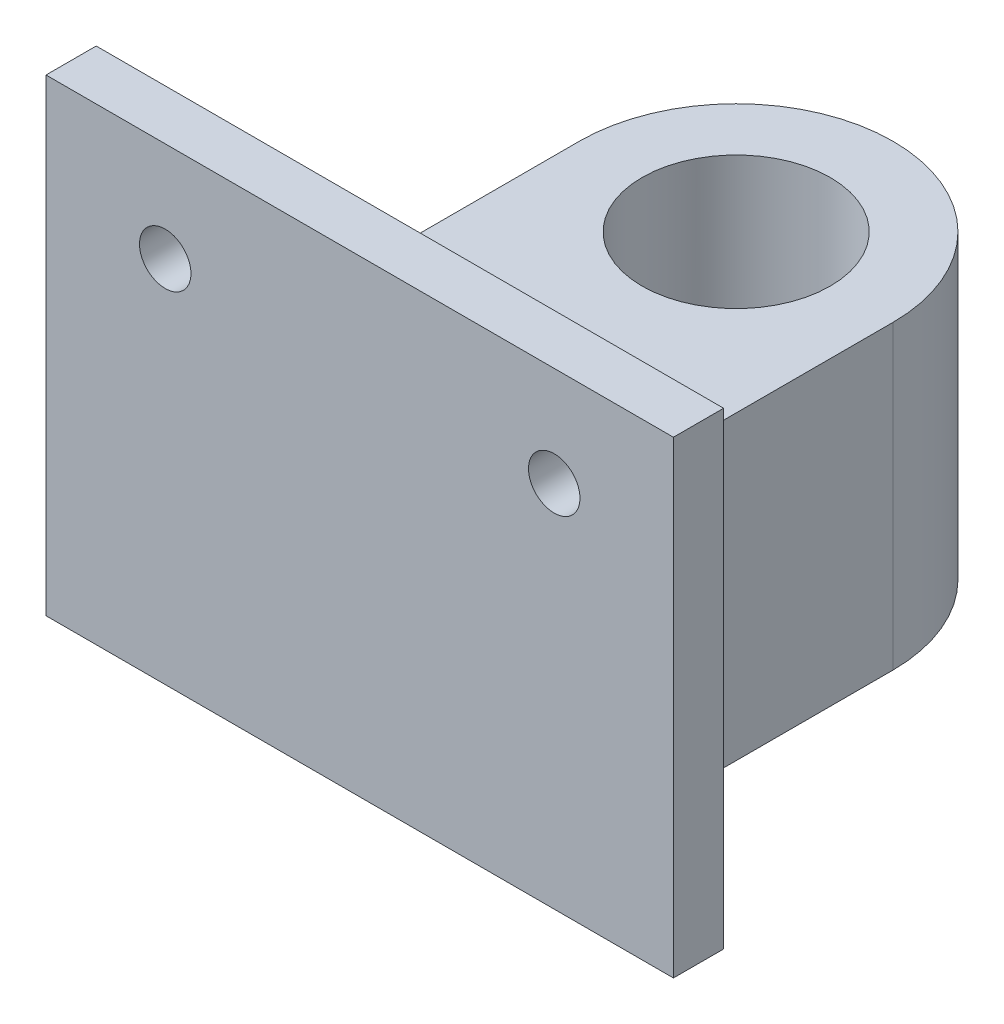
SolidWorks part; units mm, degrees
ref_plane "Front Plane" through (0, 0, 0) normal (0, 0, 1) x (1, 0, 0)
ref_plane "Top Plane" through (0, 0, 0) normal (0, 1, 0) x (1, 0, 0)
ref_plane "Right Plane" through (0, 0, 0) normal (1, 0, 0) x (0, 0, -1)
sketch "Profile-Sketch1" plane through (0, 0, 0) normal (0, 1, 0) x (1, 0, 0)
  line L0 (-25, -30) -> (25, -30)
  line L1 (25, -30) -> (25, -26)
  line L2 (-25, -30) -> (-25, -26)
  line L3 (-25, -26) -> (-22.5, -26)
  line L4 (-12.5, -16) -> (-12.5, 0)
  line L5 (25, -26) -> (22.5, -26)
  line L6 (12.5, -16) -> (12.5, 0)
  circle A0 centre (0, 0) radius 7.5
  arc A6 (12.5, 0) -> (-12.5, 0) centre (0, 0) ccw
  arc A7 (22.5, -26) -> (12.5, -16) centre (22.5, -16) cw
  arc A8 (-12.5, -16) -> (-22.5, -26) centre (-22.5, -16) cw
  dimension "D1" = 15
  dimension "D2" = 25
  dimension "D7" = 10
  dimension "D3" = 50
  dimension "D4" = 25
  dimension "D5" = 30
  dimension "D6" = 4
extrude "Profile-Boss-Extrude2" add sketch "Profile-Sketch1" along normal blind 37.3224
sketch "FasteningHoleSketch3" plane through (0, 0, 30) normal (0, 0, 1) x (1, 0, 0)
  line L0 (25, 37.3224) -> (25, 0) construction
  line L2 (-25, 0) -> (25, 0) construction
  circle A2 centre (-15.5, 29.3849) radius 2.05
  circle A3 centre (15.5, 29.3849) radius 2.05
  dimension "D3" = 4.1
  dimension "D2" = 29.3849
  dimension "D1" = 9.5
  dimension "D4" = 31
extrude "FasteningHoleCut-Extrude8" cut sketch "FasteningHoleSketch3" against normal through all
sketch "LM8UUPlugSketch1" plane through (0, 0, 0) normal (0, -1, 0) x (1, 0, 0)
  circle A0 centre (0, 0) radius 7.5
  circle A1 centre (0, 0) radius 7.5 construction
  circle A2 centre (0, 0) radius 4.5
extrude "LM8UU plugBoss-Extrude1" add sketch "LM8UUPlugSketch1" along normal blind 0.0001 and the other way blind 1
sketch "Sketch2" plane through (0, 37.3224, 0) normal (0, 1, 0) x (1, 0, 0)
  line L0 (-12.5, 0) -> (-12.5, -16)
  line L1 (12.5, 0) -> (12.5, -16)
  line L2 (-22.5, -26) -> (22.5, -26)
  arc A0 (12.5, 0) -> (-12.5, 0) centre (0, 0) ccw
  arc A1 (12.5, 0) -> (-12.5, 0) centre (0, 0) ccw construction
  arc A2 (-22.5, -26) -> (-12.5, -16) centre (-22.5, -16) ccw
  arc A3 (-22.5, -26) -> (-12.5, -16) centre (-22.5, -16) ccw construction
  arc A4 (12.5, -16) -> (22.5, -26) centre (22.5, -16) ccw
  arc A5 (12.5, -16) -> (22.5, -26) centre (22.5, -16) ccw construction
extrude "Cut-Extrude1" cut sketch "Sketch2" against normal blind 13.3224
equation "\"RailThickness\"= .125in'Spec"
equation "\"LM8UUDiameter\"= 15mm"
equation "\"MidLeftOrRightSideRailHeight\"= 2.0in"
equation "\"RodStabilizerLength\"= 50mm"
equation "\"HoleOffsetFromEdge\"= \"RailThickness\" * 2.5"
equation "\"Nema17StepperMountSlotDistance\"= 31mm'Spec"
equation "\"LM8UUHeight\"= 24mm'Spec"
equation "\"V1 BottomOfLowerRail\"= \"LegHeight\""
equation "\"RodStabilizerHeight\"= \"V8 ToTopOfMidSideRailYSValue\" - \"MidLeftOrRightSideRailHeight\" - \"V2 ToBedAtTopOfZAxisYSValue\" + \"MidLeftOrRightSideRailHeight\" / 2 + \"RailThickness\" * 1.5 + .77517'Equals 37.32237. Add .77517 for LM8UU to be at bottom of RodStabilizer"
equation "\"D1@Profile-Sketch1\"= \"LM8UUDiameter\""
equation "\"D3@Profile-Sketch1\" = \"RodStabilizerLength\""
equation "\"D4@Profile-Sketch1\" = \"RodStabilizerLength\" / 2"
equation "\"D6@Profile-Sketch1\" = \"M3HeatInsertHoleDepth\""
equation "\"D1@Profile-Boss-Extrude2\"= \"RodStabilizerHeight\""
equation "\"V8 ToTopOfMidSideRailYSValue\"= 376.9847mm"
equation "\"D5@Profile-Sketch1\"=\"Nema17MountStepperHoleFromBack\""
equation "\"RodStabilizerMountingHoleYOffsetFromBottom\"= \"RodStabilizerHeight\" - \"HoleOffsetFromEdge\""
equation "\"D2@FasteningHoleSketch3\"=\"RodStabilizerMountingHoleYOffsetFromBottom\""
equation "\"D3@FasteningHoleSketch3\"=\"M3HeatInsertHoleDiameter\""
equation "\"M3HeatInsertHoleDiameter\"= 4mm + .1mm'Add .1mm for printing"
equation "\"D1@Cut-Extrude1\"=\"RodStabilizerHeight\"-\"LM8UUHeight\""
equation "\"8mmLeadScrewHoleDiameter\"= 8mm + 1mm'Add 1mm for spacing"
equation "\"D1@LM8UUPlugSketch1\"=\"8mmLeadScrewHoleDiameter\""
equation "\"D4@FasteningHoleSketch3\"=\"Nema17StepperMountSlotDistance\""
equation "\"D1@FasteningHoleSketch3\"=(\"RodStabilizerLength\" - \"Nema17StepperMountSlotDistance\")/2"
equation "\"Nema17MountStepperHoleFromBack\"= 30mm"
equation "\"M3HeatInsertHoleDepth\"= 4mm"
equation "\"V2 ToBedAtTopOfZAxisYSValue\"= 319.8mm"
